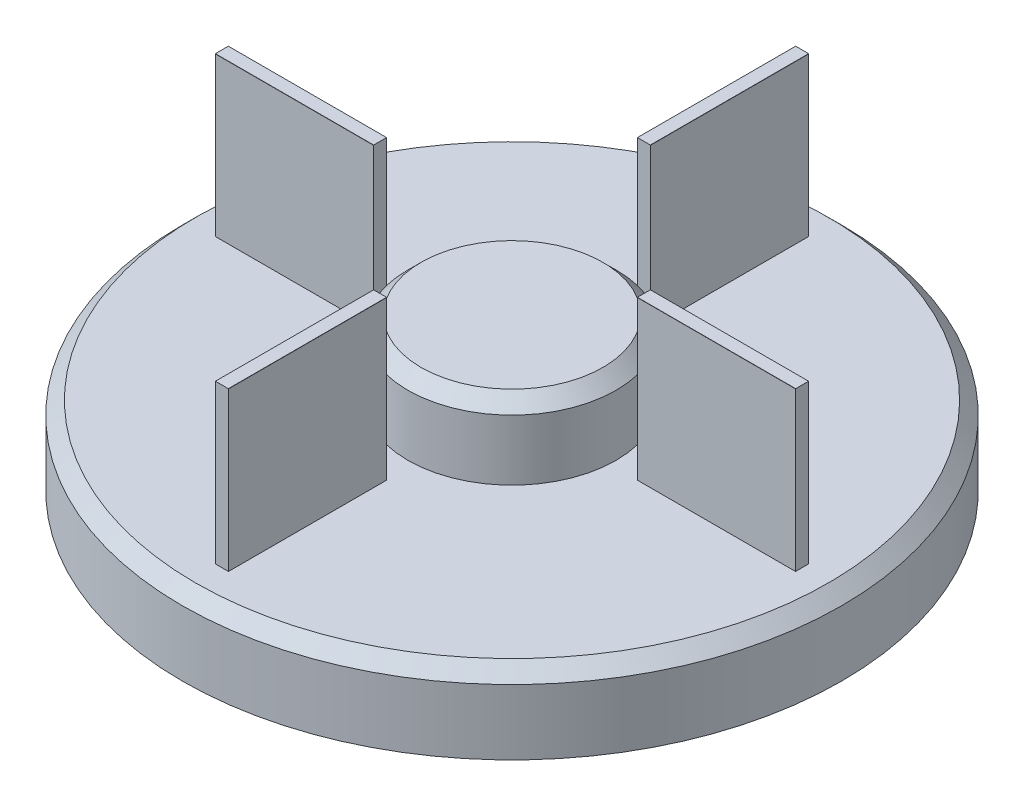
SolidWorks part; units mm, degrees
material "Brass"
ref_plane "Front Plane" through (0, 0, 0) normal (0, 0, 1) x (1, 0, 0)
ref_plane "Top Plane" through (0, 0, 0) normal (0, 1, 0) x (1, 0, 0)
ref_plane "Right Plane" through (0, 0, 0) normal (1, 0, 0) x (0, 0, -1)
sketch "Sketch1" plane through (0, 0, 0) normal (0, 1, 0) x (1, 0, 0)
  circle A0 centre (0, 0) radius 25
  dimension "D1" = 50
extrude "Boss-Extrude1" add sketch "Sketch1" along normal blind 5.95 contours A0
sketch "Sketch2" plane through (0, 5.95, 0) normal (0, 1, 0) x (1, 0, 0)
  circle A0 centre (0, 0) radius 7.9
  dimension "D1" = 15.8
extrude "Boss-Extrude2" add sketch "Sketch2" along normal blind 5.6 contours A0
chamfer "Chamfer2" distance 1 angle 45 1 edges at (0, 5.95, 25)
sketch "Sketch4" plane through (0, 5.95, 0) normal (0, 1, 0) x (1, 0, 0)
  line L0 (0, 0) -> (0, -16) construction
  line L1 (-22, -0.5) -> (-10, -0.5)
  line L2 (-0.5, -22) -> (0.5, -22)
  line L3 (-0.5, -22) -> (-0.5, -10)
  line L4 (-0.5, -10) -> (0.5, -10)
  line L5 (0.5, -22) -> (0.5, -10)
  line L6 (-0.5, -22) -> (0.5, -10) construction
  line L7 (-0.5, -10) -> (0.5, -22) construction
  line L8 (-22, 0.5) -> (-10, 0.5)
  line L9 (-10, 0.5) -> (-10, -0.5)
  line L10 (-22, 0.5) -> (-22, -0.5)
  line L11 (-0.5, 22) -> (-0.5, 10)
  line L12 (0.5, 22) -> (0.5, 10)
  line L13 (0.5, 10) -> (-0.5, 10)
  line L14 (0.5, 22) -> (-0.5, 22)
  line L15 (22, 0.5) -> (10, 0.5)
  line L16 (22, -0.5) -> (10, -0.5)
  line L17 (10, -0.5) -> (10, 0.5)
  line L18 (22, -0.5) -> (22, 0.5)
  point P22 (0, 0)
  dimension "D1" = 16
  dimension "D2" = 12
  dimension "D3" = 1
  dimension "D4" = 4
extrude "Boss-Extrude3" add sketch "Sketch4" along normal blind 12
chamfer "Chamfer3" distance 1 angle 45 1 edges at (0, 11.55, 7.9)
chamfer "Chamfer4" distance 0.01 angle 45 8 edges at (0.5, 17.95, 16) (-0.5, 17.95, 16) (16, 17.95, 0.5) (16, 17.95, -0.5) (0.5, 17.95, -16) (-16, 17.95, -0.5) (-0.5, 17.95, -16) (-16, 17.95, 0.5)
sketch "Sketch5" plane through (0, 0, 0) normal (0, -1, 0) x (-1, 0, 0)
  circle A0 centre (0, 0) radius 24
  circle A1 centre (0, 0) radius 8
  dimension "D1" = 48
  dimension "D2" = 16
extrude "Cut-Extrude5" cut sketch "Sketch5" against normal blind 2
fillet "Fillet1" radius 10 1 edges at (0, 0, -8)
sketch "Sketch6" plane through (0, 0, 0) normal (0, -1, 0) x (1, 0, 0)
  circle A1 centre (0, 0) radius 2
  circle A2 centre (0, 0) radius 2
  dimension "D1" = 0
extrude "Cut-Extrude6" cut sketch "Sketch6" against normal blind 5
thread "Thread1" pitch 1 method cut profile "Thread Profile1" start angle 0, offset 0, length 10, pitch 1, diameter 4
ref_plane "Plane1" through (2, 0, 0) normal (0, 0, 1) x (1, 0, 0)
sketch "Thread Profile1" plane through (2, 0, 0) normal (0, 0, 1) x (1, 0, 0)
  line L0 (0, 0) -> (0, 1) construction
  line L1 (0, 0) -> (0.5413, 0.3125)
  line L2 (0.5413, 0.3125) -> (0.5413, 0.4375)
  line L3 (0.5413, 0.4375) -> (0, 0.75)
  line L4 (0.5413, 0.375) -> (0, 0.375) construction
  line L11 (0, 0) -> (0, 0.75)
  point P2 (0, 0)
  dimension "Pitch" = 1
  dimension "Profile_Angle" = 60
  dimension "Profile_Land" = 0.125
  dimension "Profile_Height" = 0.5413
sketch "Sketch9" plane through (0, 0, 0) normal (0, 0, -1) x (-1, 0, 0)
  line L0 (0, 0) -> (0.0658, -0.9822)
  line L4 (-2.5413, 0.4375) -> (-2.5413, 0.3125)
  line L5 (-2.5413, 0.3125) -> (-2, 0)
  line L6 (-2, 0) -> (-2, 0.75)
  line L7 (-2, 0.75) -> (-2.5413, 0.4375)
  line L8 (-2.5413, 0.4375) -> (-2.5413, 0.3125)
  line L9 (-2.5413, 0.3125) -> (-2, 0)
  line L10 (-2, 0) -> (-2, 0.75)
  line L11 (-2, 0.75) -> (-2.5413, 0.4375)
  dimension "D1" = 0
